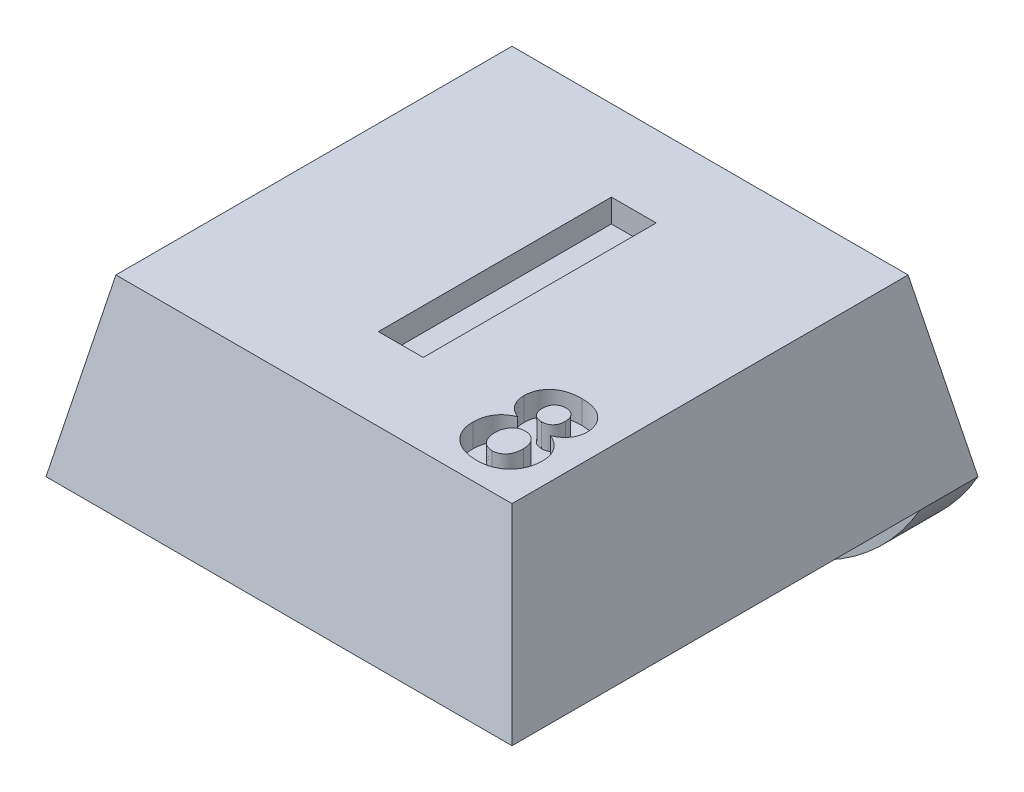
SolidWorks part; units mm, degrees
ref_plane "Front Plane" through (0, 0, 0) normal (0, 0, 1) x (1, 0, 0)
ref_plane "Top Plane" through (0, 0, 0) normal (0, 1, 0) x (1, 0, 0)
ref_plane "Right Plane" through (0, 0, 0) normal (1, 0, 0) x (0, 0, -1)
sketch "Sketch1" plane through (0, 0, 0) normal (0, 1, 0) x (1, 0, 0)
  line L1 (0, 0) -> (8, 0)
  line L2 (0, 0) -> (0, 8)
  line L3 (0, 8) -> (8, 8)
  line L4 (8, 0) -> (8, 8)
  dimension "D1" = 8
  dimension "D2" = 8
extrude "Boss-Extrude1" add sketch "Sketch1" along normal blind 3
sketch "Sketch2" plane through (0, 0, 0) normal (0, 0, 1) x (1, 0, 0)
  line L0 (0, 0) -> (0.6, 3)
  line L1 (0, 3) -> (8, 3) construction
  line L2 (0.6, 3) -> (0, 3)
  line L3 (0, 3) -> (0, 0)
  line L4 (8, 0) -> (7.4, 3)
  line L5 (7.4, 3) -> (8, 3)
  line L6 (8, 3) -> (8, 0)
  dimension "D1" = 0.6
  dimension "D2" = 0.6
extrude "Cut-Extrude1" cut sketch "Sketch2" against normal through all both and the other way through all
sketch "Sketch3" plane through (0, 0, 0) normal (1, 0, 0) x (0, 0, -1)
  line L0 (0, 0) -> (0.6, 3)
  line L1 (8, 3) -> (0, 3) construction
  line L2 (0.6, 3) -> (0, 3)
  line L3 (0, 3) -> (0, 0)
  line L4 (8, 3) -> (7.4, 3)
  line L5 (7.4, 3) -> (8, 0)
  line L6 (8, 3) -> (8, 0)
  dimension "D1" = 0.6
  dimension "D2" = 0.6
extrude "Cut-Extrude2" cut sketch "Sketch3" along normal blind 11
sketch "Sketch4" plane through (0, 0, 0) normal (0, -1, 0) x (1, 0, 0)
  line L0 (8, 0) -> (8, -8) construction
  line L3 (0, 0) -> (8, 0) construction
  circle A0 centre (4, -3.75) radius 1.8
  dimension "D1" = 3.6
  dimension "D2" = 4
  dimension "D3" = 3.75
extrude "Cut-Extrude3" cut sketch "Sketch4" against normal blind 0.8
sketch "Sketch5" plane through (0, 0, 0) normal (0, -1, 0) x (1, 0, 0)
  line L0 (8, 0) -> (8, -8) construction
  line L1 (0, -8) -> (8, -8)
  line L2 (0, -8) -> (0, -7)
  line L3 (0, -7) -> (8, -7)
  line L4 (8, -8) -> (8, -7)
  dimension "D1" = 1
extrude "Boss-Extrude2" add sketch "Sketch5" along normal blind 2
fillet "Fillet1" radius 4 2 edges at (8, -2, -7.5) (0, -2, -7.5)
sketch "Sketch6" plane through (0, 3, 0) normal (0, 1, 0) x (1, 0, 0)
  text T0 "I" font "Arial" height 4
extrude "Cut-Extrude4" cut sketch "Sketch6" against normal blind 0.4
sketch "Sketch7" plane through (0, 3, 0) normal (0, 1, 0) x (1, 0, 0)
  text T0 "8" font "Arial" height 1.8
extrude "Cut-Extrude5" cut sketch "Sketch7" against normal blind 0.4
